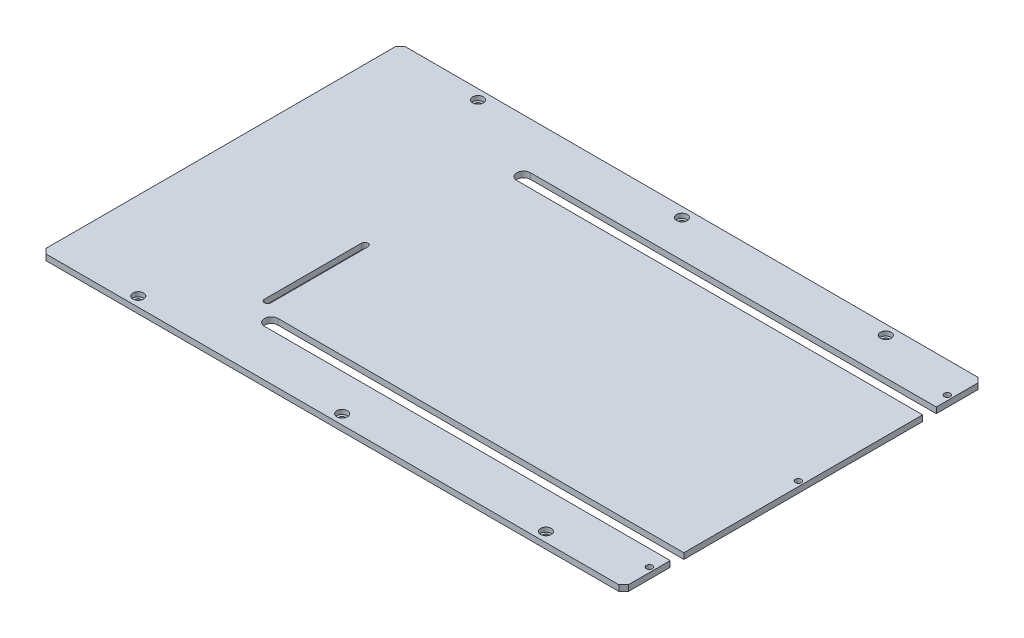
SolidWorks part; units mm, degrees
ref_plane "정면" through (0, 0, 0) normal (0, 0, 1) x (1, 0, 0)
ref_plane "윗면" through (0, 0, 0) normal (0, 1, 0) x (1, 0, 0)
ref_plane "우측면" through (0, 0, 0) normal (1, 0, 0) x (0, 0, -1)
sketch "스케치1" plane through (0, 0, 0) normal (0, 1, 0) x (1, 0, 0)
  line L1 (0, 0) -> (300, 0)
  line L2 (0, 0) -> (0, 185)
  line L3 (0, 185) -> (300, 185)
  line L4 (300, 0) -> (300, 185)
  dimension "D1" = 185
  dimension "D2" = 300
extrude "보스-돌출1" add sketch "스케치1" along normal blind 3
sketch "스케치2" plane through (0, 3, 0) normal (0, 1, 0) x (1, 0, 0)
  line L0 (93, 61.1066) -> (93.0904, 61.1066) construction
  line L1 (93, 58.6066) -> (93, 63.6066) construction
  line L3 (78.9, 61.1066) -> (78.9, 86.1066)
  line L4 (78.9, 36.1066) -> (82.2, 36.1066)
  line L5 (78.9, 36.1066) -> (78.9, 61.1066)
  line L6 (78.9, 86.1066) -> (82.2, 86.1066)
  line L7 (82.2, 36.1066) -> (82.2, 86.1066)
  line L8 (80.1, 81.2292) -> (80.1, 83.4866) construction
  line L10 (81, 81.2292) -> (81, 83.4866) construction
  dimension "D1" = 1.2
  dimension "D2" = 1.2
  dimension "D3" = 25
  dimension "D4" = 25
extrude "컷-돌출1" cut sketch "스케치2" against normal blind 10
sketch "스케치3" plane through (0, 3, 0) normal (0, 1, 0) x (1, 0, 0)
  line L0 (82.2, 86.1066) -> (78.9, 86.1066) construction
  line L1 (78.9, 36.1066) -> (82.2, 36.1066) construction
  circle A0 centre (80.55, 86.1066) radius 1.65
  circle A1 centre (80.55, 36.1066) radius 1.65
extrude "컷-돌출2" cut sketch "스케치3" against normal blind 10
sketch "스케치4" plane through (0, 3, 0) normal (0, 1, 0) x (1, 0, 0)
  line L0 (98.3962, 160) -> (115.2566, 160) construction
  line L1 (300, 161) -> (91, 161)
  line L2 (300, 161) -> (300, 154)
  line L3 (300, 154) -> (91, 154)
  line L4 (91, 161) -> (91, 154)
  line L5 (91, 24) -> (300, 24)
  line L6 (91, 24) -> (91, 31)
  line L7 (91, 31) -> (300, 31)
  line L8 (300, 24) -> (300, 31)
  line L9 (98.3962, 155) -> (115.2566, 155) construction
  line L10 (98.3962, 30) -> (115.2566, 30) construction
  line L13 (300, 0) -> (300, 185) construction
  dimension "D1" = 1
  dimension "D2" = 1
  dimension "D3" = 1
  dimension "D4" = 10
extrude "컷-돌출3" cut sketch "스케치4" against normal blind 10
sketch "스케치5" plane through (0, 3, 0) normal (0, 1, 0) x (1, 0, 0)
  line L0 (91, 161) -> (91, 154) construction
  line L3 (91, 31) -> (91, 24) construction
  circle A0 centre (91, 157.5) radius 3.5
  circle A3 centre (91, 27.5) radius 3.5
extrude "컷-돌출5" cut sketch "스케치5" against normal blind 10
sketch "스케치6" plane through (0, 0, 0) normal (0, -1, 0) x (1, 0, 0)
  line L0 (297.5, -17.3) -> (297.5, -14.2) construction
  line L1 (295, -17.3) -> (300, -17.3) construction
  line L2 (295, -14.2) -> (300, -14.2) construction
  line L3 (297.5, -90.95) -> (297.5, -94.05) construction
  line L6 (297.5, -170.75) -> (297.5, -167.65) construction
  line L7 (295, -170.75) -> (300, -170.75) construction
  line L8 (295, -167.65) -> (300, -167.65) construction
  line L9 (295, -90.95) -> (300, -90.95) construction
  line L10 (295, -94.05) -> (300, -94.05) construction
  circle A0 centre (297.5, -169.2) radius 1.55
  circle A1 centre (297.5, -92.5) radius 1.55
  circle A2 centre (297.5, -15.75) radius 1.55
extrude "컷-돌출6" cut sketch "스케치6" against normal blind 10
sketch "스케치7" plane through (0, 0, 0) normal (0, -1, 0) x (-1, 0, 0)
  line L0 (-46.55, 180) -> (-43.45, 180) construction
  line L3 (-148.45, 180) -> (-151.55, 180) construction
  line L4 (-148.45, 177.5) -> (-148.45, 182.5) construction
  line L5 (-151.55, 177.5) -> (-151.55, 182.5) construction
  line L6 (-256.55, 180) -> (-253.45, 180) construction
  line L10 (-256.55, 177.5) -> (-256.55, 182.5) construction
  line L11 (-253.45, 177.5) -> (-253.45, 182.5) construction
  line L12 (-46.55, 177.5) -> (-46.55, 182.5) construction
  line L13 (-43.45, 177.5) -> (-43.45, 182.5) construction
  line L14 (0, 92.5) -> (-300, 92.5) construction
  line L15 (0, 185) -> (0, 0) construction
  line L16 (-300, 31) -> (-300, 154) construction
  line L17 (-256.55, 5) -> (-253.45, 5) construction
  line L18 (-148.45, 5) -> (-151.55, 5) construction
  line L19 (-46.55, 5) -> (-43.45, 5) construction
  circle A0 centre (-255, 180) radius 1.55
  circle A1 centre (-150, 180) radius 1.55
  circle A2 centre (-45, 180) radius 1.55
  circle A3 centre (-45, 5) radius 1.55
  circle A4 centre (-150, 5) radius 1.55
  circle A5 centre (-255, 5) radius 1.55
extrude "컷-돌출8" cut sketch "스케치7" against normal blind 10
sketch "스케치8" plane through (0, 3, 0) normal (0, 1, 0) x (1, 0, 0)
  circle A0 centre (45, 5) radius 2.75
  circle A1 centre (150, 5) radius 2.75
  circle A2 centre (255, 5) radius 2.75
  circle A3 centre (255, 180) radius 2.75
  circle A4 centre (150, 180) radius 2.75
  circle A5 centre (45, 180) radius 2.75
  dimension "D1" = 5.5
extrude "컷-돌출9" cut sketch "스케치8" against normal blind 2.3
chamfer "모따기1" distance 2.5 angle 45 4 edges at (0, 1.5, 0) (0, 1.5, -185) (300, 1.5, 0) (300, 1.5, -185)
